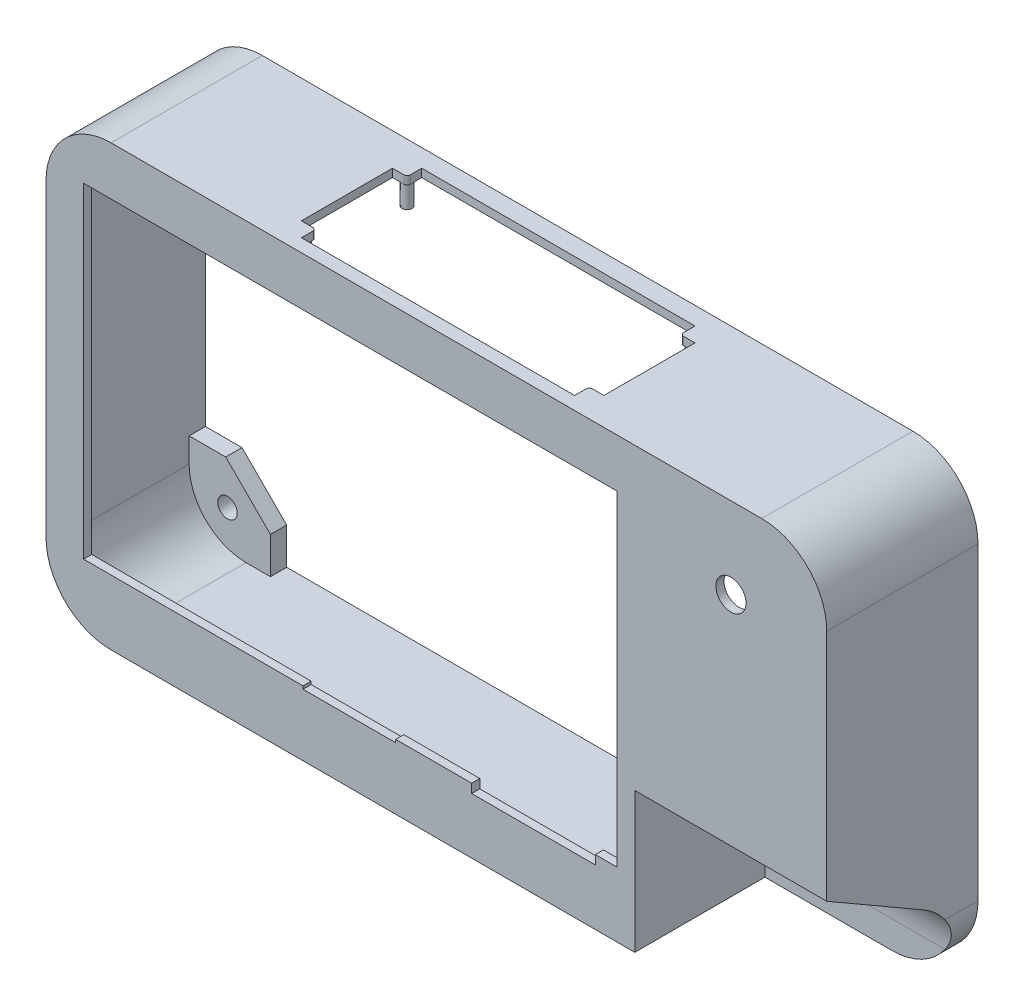
SolidWorks part; units mm, degrees
ref_plane "Front Plane" through (0, 0, 0) normal (0, 0, 1) x (1, 0, 0)
ref_plane "Top Plane" through (0, 0, 0) normal (0, 1, 0) x (1, 0, 0)
ref_plane "Right Plane" through (0, 0, 0) normal (1, 0, 0) x (0, 0, -1)
sketch "Sketch2" plane through (0, 0, 0) normal (0, 0, 1) x (1, 0, 0)
  line L1 (-100, -67.5) -> (100, -67.5)
  line L2 (-120, -47.5) -> (-120, 47.5)
  line L3 (-100, 67.5) -> (100, 67.5)
  line L4 (120, -47.5) -> (120, 47.5)
  line L5 (-120, -67.5) -> (120, 67.5) construction
  line L6 (-120, 67.5) -> (120, -67.5) construction
  arc A0 (100, 67.5) -> (120, 47.5) centre (100, 47.5) cw
  arc A1 (100, -67.5) -> (120, -47.5) centre (100, -47.5) ccw
  arc A2 (-100, -67.5) -> (-120, -47.5) centre (-100, -47.5) cw
  arc A3 (-120, 47.5) -> (-100, 67.5) centre (-100, 47.5) cw
  point P0 (0, 0)
  dimension "D2" = 20
  dimension "D1" = 135
  dimension "25" = 240
extrude "Boss-Extrude1" add sketch "Sketch2" along normal mid plane 80
sketch "Sketch3" plane through (0, 0, 40) normal (0, 0, 1) x (1, 0, 0)
  line L0 (61, -67.5) -> (61, -9.3428)
  line L1 (-100, -67.5) -> (100, -67.5) construction
  line L2 (61, -9.3428) -> (120, -9.3428)
  line L3 (120, -47.5) -> (120, 47.5) construction
  line L4 (120, -9.3428) -> (120, -47.5)
  line L5 (100, -67.5) -> (61, -67.5)
  line L6 (120, -47.5) -> (61, -47.5)
  arc A0 (100, -67.5) -> (120, -47.5) centre (100, -47.5) ccw construction
  arc A1 (100, -67.5) -> (120, -47.5) centre (100, -47.5) ccw
  line M11 (-100, -67.5) -> (100, -67.5)
  arc M12 (100, -67.5) -> (120, -47.5) centre (100, -47.5) ccw
  dimension "D1" = 59
extrude "Cut-Extrude2" cut sketch "Sketch3" against normal blind 40 contours L6 L0 M12 M11 region at (88.5361, -57.0659, 40)
sketch "Sketch4" plane through (120, 0, 0) normal (1, 0, 0) x (0, 0, -1)
  line L0 (0, -47.5) -> (-40, -24.406)
  line L1 (-40, -47.5) -> (-40, 47.5) construction
  line L2 (-40, -47.5) -> (0, -47.5) construction
  line L3 (-40, -24.406) -> (-40, -47.5)
  line L4 (-40, -47.5) -> (0, -47.5)
  dimension "D1" = 30
extrude "Cut-Extrude3" cut sketch "Sketch4" against normal blind 59
shell "Shell2" thickness 2.5 removed face at (0, 0, -40)
sketch "Sketch5" plane through (0, -35.625, 20.5681) normal (0, -0.866, 0.5) x (1, 0, 0)
  line L0 (61, 22.438) -> (120, 22.438) construction
  line L1 (120, -23.75) -> (61, -23.75) construction
  line L3 (78.4748, 17.8994) -> (101.1248, 17.8994)
  line L4 (78.4748, 17.8994) -> (78.4748, 3.7994)
  line L5 (90.5, -0.656) -> (120, -0.656) construction
  line L6 (90.5, -0.656) -> (61, -0.656) construction
  line L9 (120, -23.75) -> (120, 22.438)
  line L10 (120, 22.438) -> (61, 22.438)
  line L11 (61, 22.438) -> (61, -23.75)
  line L12 (61, -23.75) -> (120, -23.75)
  line L13 (120, -23.75) -> (120, -0.656)
  line L14 (120, 22.438) -> (61, 22.438)
  line L15 (61, 22.438) -> (61, -23.75)
  line L16 (61, -23.75) -> (120, -23.75)
  line L19 (78.4748, 3.7994) -> (101.1248, 3.7994)
  line L21 (78.4748, 5.7549) -> (78.4748, 3.7994)
  line L27 (101.1248, 17.8994) -> (101.1248, 3.7994)
  line L35 (101.1248, 5.7549) -> (101.1248, 3.7994)
  line L37 (120, -23.75) -> (120, 22.438) construction
  circle A0 centre (90.5, -0.656) radius 23.094
  dimension "D4" = 18.8752
  dimension "D5" = 17.4748
  dimension "D6" = 18.8752
  dimension "D7" = 17.4748
  dimension "D1" = 0
sketch "Sketch7" plane through (0, -35.625, 20.5681) normal (0, -0.866, 0.5) x (1, 0, 0)
  line L0 (101.1248, 17.8994) -> (101.1248, 3.7994) construction
  line L1 (78.4748, 3.7994) -> (101.1248, 3.7994) construction
  line L2 (78.4748, 17.8994) -> (101.1248, 17.8994) construction
  line L3 (78.4748, 17.8994) -> (78.4748, 3.7994) construction
  line L4 (101.1248, 17.8994) -> (101.1248, 3.7994)
  line L5 (78.4748, 3.7994) -> (101.1248, 3.7994)
  line L6 (78.4748, 17.8994) -> (101.1248, 17.8994)
  line L7 (78.4748, 17.8994) -> (78.4748, 3.7994)
extrude "Cut-Extrude8" cut sketch "Sketch5" against normal blind 5 contours L35 L21 region at (89.7998, -30.2003, 29.964)
sketch "Sketch8" plane through (0, 0, 37.5) normal (0, 0, -1) x (-1, 0, 0)
  line L1 (-105.6, 50.5) -> (-100.6, 50.5)
  line L2 (-105.6, 50.5) -> (-105.6, 55.5)
  line L3 (-105.6, 55.5) -> (-100.6, 55.5)
  line L4 (-100.6, 50.5) -> (-100.6, 55.5)
  line L5 (-103.8071, 52.2929) -> (-102.3929, 53.7071) construction
  line L6 (-58.5, -22.9626) -> (-58.5, -65)
  line L7 (-58.5, -65) -> (100, -65)
  line L8 (117.5, -47.5) -> (117.5, 47.5)
  line L9 (100, 65) -> (-100, 65)
  line L10 (-117.5, 47.5) -> (-117.5, -22.9626)
  line L11 (-117.5, -22.9626) -> (-58.5, -22.9626)
  line L12 (-58.5, -22.9626) -> (-58.5, -65)
  line L13 (-58.5, -65) -> (100, -65)
  line L14 (117.5, -47.5) -> (117.5, 47.5)
  line L15 (100, 65) -> (-100, 65)
  line L16 (-117.5, 47.5) -> (-117.5, -22.9626)
  line L17 (-117.5, -22.9626) -> (-58.5, -22.9626)
  line L18 (-103.8071, 53.7071) -> (-102.3929, 52.2929) construction
  line L19 (-93.1, 50.5) -> (-88.1, 50.5)
  line L20 (-93.1, 50.5) -> (-93.1, 55.5)
  line L21 (-93.1, 55.5) -> (-88.1, 55.5)
  line L22 (-88.1, 50.5) -> (-88.1, 55.5)
  line L23 (-91.3071, 52.2929) -> (-89.8929, 53.7071) construction
  line L24 (-91.3071, 53.7071) -> (-89.8929, 52.2929) construction
  line L25 (-93.1, 29.5) -> (-88.1, 29.5)
  line L26 (-93.1, 29.5) -> (-93.1, 34.5)
  line L27 (-93.1, 34.5) -> (-88.1, 34.5)
  line L28 (-88.1, 29.5) -> (-88.1, 34.5)
  line L29 (-91.3071, 31.2929) -> (-89.8929, 32.7071) construction
  line L30 (-91.3071, 32.7071) -> (-89.8929, 31.2929) construction
  line L31 (-105.6, 29.5) -> (-100.6, 29.5)
  line L32 (-105.6, 29.5) -> (-105.6, 34.5)
  line L33 (-105.6, 34.5) -> (-100.6, 34.5)
  line L34 (-100.6, 29.5) -> (-100.6, 34.5)
  line L35 (-103.8071, 31.2929) -> (-102.3929, 32.7071) construction
  line L36 (-103.8071, 32.7071) -> (-102.3929, 31.2929) construction
  arc A3 (100, -65) -> (117.5, -47.5) centre (100, -47.5) ccw
  arc A4 (117.5, 47.5) -> (100, 65) centre (100, 47.5) ccw
  arc A5 (-100, 65) -> (-117.5, 47.5) centre (-100, 47.5) ccw
  arc A6 (100, -65) -> (117.5, -47.5) centre (100, -47.5) ccw
  arc A7 (117.5, 47.5) -> (100, 65) centre (100, 47.5) ccw
  arc A8 (-100, 65) -> (-117.5, 47.5) centre (-100, 47.5) ccw
  ellipse E0 centre (-90.6, 32) end of major axis (-89.8929, 32.7071) minor radius 1 construction
  ellipse E1 centre (-103.1, 32) end of major axis (-102.3929, 32.7071) minor radius 1 construction
  ellipse E2 centre (-103.1, 53) end of major axis (-102.3929, 53.7071) minor radius 1 construction
  ellipse E3 centre (-90.6, 53) end of major axis (-89.8929, 53.7071) minor radius 1 construction
  ellipse E4 centre (-90.6, 32) end of major axis (-89.8929, 32.7071) minor radius 1
  ellipse E5 centre (-103.1, 32) end of major axis (-102.3929, 32.7071) minor radius 1
  ellipse E6 centre (-103.1, 53) end of major axis (-102.3929, 53.7071) minor radius 1
  ellipse E7 centre (-90.6, 53) end of major axis (-89.8929, 53.7071) minor radius 1
  dimension "D2" = 5
  dimension "D1" = 0
extrude "Boss-Extrude2" add sketch "Sketch8" along normal up to surface (3.1 mm away) contours L1 L4 L3 L2 E6 | L19 L22 L21 L20 E7 | L25 L28 L27 L26 E4 | L31 L34 L33 L32 E5 region at (105.5293, 53, 37.5) region at (93.0293, 53, 37.5) region at (93.0293, 32, 37.5) region at (105.5293, 32, 37.5)
sketch "Sketch9" plane through (0, 0, 40) normal (0, 0, 1) x (1, 0, 0)
  circle A0 centre (90.55, 42.5) radius 4.6353
extrude "Cut-Extrude9" cut sketch "Sketch9" against normal blind 5
sketch "Sketch10" plane through (0, 0, 0) normal (1, 0, 0) x (0, 0, -1)
  line L1 (6.5, 80.3941) -> (74.4591, 80.3941)
  line L2 (6.5, 80.3941) -> (6.5, -88.8754)
  line L3 (6.5, -88.8754) -> (74.4591, -88.8754)
  line L4 (74.4591, 80.3941) -> (74.4591, -88.8754)
  dimension "D1" = 6.5
extrude "Cut-Extrude10" cut sketch "Sketch10" against normal through all both and the other way through all
fillet "Fillet2" radius 20 2 edges at (90.5, -47.5, 0) (88, -46.0566, -2.5)
sketch "Sketch11" plane through (0, 0, 40) normal (0, 0, 1) x (1, 0, 0)
  line L0 (10.85, -47.55) -> (10.85, -47.8) construction
  line L2 (48.85, -47.8) -> (48.85, -47.55) construction
  line L4 (-41, -47.55) -> (-41, -48.45) construction
  line L5 (-41, -48.45) -> (-12.5, -48.45) construction
  line L6 (-12.5, -48.45) -> (-12.5, -47.55) construction
  line L7 (-12.5, -47.55) -> (-41, -47.55) construction
  line L8 (-108.45, -47.55) -> (55.55, -47.55) construction
  line L9 (55.55, -47.55) -> (55.55, 52.55) construction
  line L10 (55.55, 52.55) -> (-108.45, 52.55) construction
  line L11 (-108.45, 52.55) -> (-108.45, -47.55) construction
  line L12 (10.85, -47.55) -> (10.85, -47.8)
  line L14 (48.85, -47.8) -> (48.85, -47.55)
  line L16 (-41, -47.55) -> (-41, -48.45)
  line L17 (-41, -48.45) -> (-12.5, -48.45)
  line L18 (-12.5, -48.45) -> (-12.5, -47.55)
  line L19 (-12.5, -47.55) -> (-41, -47.55)
  line L20 (-108.45, -47.55) -> (10.85, -47.55)
  line L21 (55.55, -47.55) -> (55.55, 52.55)
  line L22 (55.55, 52.55) -> (-108.45, 52.55)
  line L23 (-108.45, 52.55) -> (-108.45, -47.55)
  line L24 (10.85, -47.55) -> (10.85, -50.3)
  line L25 (48.85, -50.3) -> (10.85, -50.3) construction
  line L26 (10.85, -50.3) -> (48.85, -50.3)
  line L27 (48.85, -50.3) -> (48.85, -47.55)
  line L28 (48.85, -47.55) -> (55.55, -47.55)
extrude "Cut-Extrude11" cut sketch "Sketch11" against normal blind 15 contours L14 L28 L21 L22 L23 L20 L19 L12 L24 L26 L27 | L18 L19 L16 L17 region at (-26.0939, 2.1747, 40) region at (-26.75, -48, 40)
sketch "Sketch12" plane through (0, 67.5, 0) normal (0, 1, 0) x (1, 0, 0)
  line L12 (-49.5, -4) -> (-49.5, -31)
  line L13 (-49.5, -31) -> (-46.5, -31)
  line L14 (-45, -32.5) -> (-45, -35.5)
  line L15 (-45, -35.5) -> (38, -35.5)
  line L16 (38, -35.5) -> (38, -32.5)
  line L17 (39.5, -31) -> (42.5, -31)
  line L18 (42.5, -31) -> (42.5, -4)
  line L19 (42.5, -4) -> (39.5, -4)
  line L20 (38, -2.5) -> (38, 0.5)
  line L21 (38, 0.5) -> (-45, 0.5)
  line L22 (-45, 0.5) -> (-45, -2.5)
  line L23 (-46.5, -4) -> (-49.5, -4)
  line L31 (42.5, -4) -> (39.5, -4)
  line L48 (-50, -3.5) -> (-50, -31.5)
  line L49 (-50, -31.5) -> (-46.5, -31.5)
  line L50 (-45.5, -32.5) -> (-45.5, -36)
  line L51 (-45.5, -36) -> (38.5, -36)
  line L52 (38.5, -36) -> (38.5, -32.5)
  line L53 (39.5, -31.5) -> (43, -31.5)
  line L54 (43, -31.5) -> (43, -3.5)
  line L55 (43, -3.5) -> (39.5, -3.5)
  line L56 (38.5, -2.5) -> (38.5, 1)
  line L57 (38.5, 1) -> (-45.5, 1)
  line L58 (-45.5, 1) -> (-45.5, -2.5)
  line L59 (-46.5, -3.5) -> (-50, -3.5)
  line L60 (-50, -3.5) -> (-50, -31.5)
  line L61 (-50, -31.5) -> (-46.5, -31.5)
  line L62 (-45.5, -32.5) -> (-45.5, -36)
  line L63 (-45.5, -36) -> (38.5, -36)
  line L64 (38.5, -36) -> (38.5, -32.5)
  line L65 (39.5, -31.5) -> (43, -31.5)
  line L66 (43, -31.5) -> (43, -3.5)
  line L67 (43, -3.5) -> (39.5, -3.5)
  line L68 (38.5, -2.5) -> (38.5, 1)
  line L69 (38.5, 1) -> (-45.5, 1)
  line L70 (-45.5, 1) -> (-45.5, -2.5)
  line L71 (-46.5, -3.5) -> (-50, -3.5)
  arc A4 (-45, -32.5) -> (-46.5, -31) centre (-46.5, -32.5) ccw
  arc A5 (39.5, -31) -> (38, -32.5) centre (39.5, -32.5) ccw
  arc A6 (38, -2.5) -> (39.5, -4) centre (39.5, -2.5) ccw
  arc A7 (-46.5, -4) -> (-45, -2.5) centre (-46.5, -2.5) ccw
  arc A16 (-45.5, -32.5) -> (-46.5, -31.5) centre (-46.5, -32.5) ccw
  arc A17 (39.5, -31.5) -> (38.5, -32.5) centre (39.5, -32.5) ccw
  arc A18 (38.5, -2.5) -> (39.5, -3.5) centre (39.5, -2.5) ccw
  arc A19 (-46.5, -3.5) -> (-45.5, -2.5) centre (-46.5, -2.5) ccw
  arc A20 (-45.5, -32.5) -> (-46.5, -31.5) centre (-46.5, -32.5) ccw
  arc A21 (39.5, -31.5) -> (38.5, -32.5) centre (39.5, -32.5) ccw
  arc A22 (38.5, -2.5) -> (39.5, -3.5) centre (39.5, -2.5) ccw
  arc A23 (-46.5, -3.5) -> (-45.5, -2.5) centre (-46.5, -2.5) ccw
  dimension "D1" = 0
  dimension "D2" = 0.5
extrude "Cut-Extrude12" cut sketch "Sketch12" against normal blind 7 contours A23 L71 L60 L61 A20 L62 L63 L64 A21 L65 L66 L67 A22 L68 L69 L70 region at (-48.25, 67.5, 3.6001) body kept at (-120, -47.5, 40)
sketch "Sketch13" plane through (0, 65, 0) normal (0, -1, 0) x (1, 0, 0)
  circle A0 centre (40.25, 33.25) radius 1.5 construction
  circle A1 centre (-47.25, 33.25) radius 1.5 construction
  circle A2 centre (-47.25, 1.75) radius 1.5 construction
  circle A3 centre (40.25, 1.75) radius 1.5 construction
  circle A4 centre (40.25, 33.25) radius 1.5
  circle A5 centre (-47.25, 33.25) radius 1.5
  circle A6 centre (-47.25, 1.75) radius 1.5
  circle A7 centre (40.25, 1.75) radius 1.5
extrude "Boss-Extrude3" add sketch "Sketch13" along normal blind 7
sketch "Sketch14" plane through (0, -33.4599, 19.3181) normal (0, 0.866, -0.5) x (1, 0, 0)
  line L1 (101.1248, -3.7994) -> (78.3799, -3.7994)
  line L2 (101.1248, -3.7994) -> (101.1248, -2.4204)
  line L3 (101.1248, -2.4204) -> (78.3799, -2.4204)
  line L4 (78.3799, -3.7994) -> (78.3799, -2.4204)
extrude "Boss-Extrude4" add sketch "Sketch14" along normal blind 16
sketch "Sketch15" plane through (0, 1.8997, 3.2904) normal (0, 0.5, 0.866) x (1, 0, 0)
  circle A0 centre (81.4748, -27.3362) radius 1 construction
  circle A1 centre (98.1248, -27.3362) radius 1 construction
  circle A2 centre (81.4748, -27.3362) radius 1
  circle A3 centre (98.1248, -27.3362) radius 1
extrude "Cut-Extrude13" cut sketch "Sketch15" against normal blind 6
sketch "Sketch16" plane through (0, -19.6035, 11.3181) normal (0, 0.866, -0.5) x (1, 0, 0)
  line L0 (101.1248, -2.4204) -> (78.3799, -2.4204) construction
  line L1 (92.6039, -2.4204) -> (86.9008, -2.4204)
  line L2 (92.6039, -2.4204) -> (92.6039, -3.7994)
  line L3 (92.6039, -3.7994) -> (86.9008, -3.7994)
  line L4 (86.9008, -2.4204) -> (86.9008, -3.7994)
  line L5 (78.3799, -3.7994) -> (101.1248, -3.7994) construction
  line L6 (101.1248, -2.4204) -> (92.6039, -2.4204) construction
  line L7 (86.9008, -2.4204) -> (78.3799, -2.4204) construction
sketch "Sketch17" plane through (0, 1.2102, 2.0962) normal (0, -0.5, -0.866) x (-1, 0, 0)
  line L0 (-78.3799, -22.6362) -> (-78.3799, -38.6362) construction
  line L1 (-98.1248, -35.6362) -> (-81.3799, -35.6362)
  line L2 (-98.1248, -35.6362) -> (-98.1248, -30.6651)
  line L3 (-98.1248, -30.6651) -> (-81.3799, -30.6651)
  line L4 (-81.3799, -35.6362) -> (-81.3799, -30.6651)
  line L5 (-101.1248, -22.6362) -> (-101.1248, -38.6362) construction
  line L7 (-117.5, -38.6362) -> (-58.5, -38.6362) construction
  line L8 (-101.1248, -22.6362) -> (-78.3799, -22.6362) construction
  line L9 (-95.6248, -30.6651) -> (-83.9748, -30.6651)
  line L10 (-95.6248, -30.6651) -> (-95.6248, -25.6362)
  line L11 (-95.6248, -25.6362) -> (-83.9748, -25.6362)
  line L12 (-83.9748, -30.6651) -> (-83.9748, -25.6362)
  circle A1 centre (-98.1248, -27.3362) radius 1 construction
  circle A2 centre (-81.4748, -27.3362) radius 1 construction
  dimension "D5" = 2.5
  dimension "D1" = 3
  dimension "D2" = 3
  dimension "D3" = 3
  dimension "D4" = 3
  dimension "D6" = 2.5
extrude "Cut-Extrude14" cut sketch "Sketch17" against normal blind 6 contours L1 L4 L3 L2 | L3 L12 L11 L10 region at (89.7523, -27.4991, 18.6715) region at (89.7998, -23.169, 16.1715)
extrude "Boss-Extrude5" add sketch "Sketch16" along normal blind 25
sketch "Sketch19" plane through (86.9008, 0, 0) normal (-1, 0, 0) x (0, 0, 1)
  line L0 (3.4143, -1.0728) -> (4.6085, -0.3833)
  line L1 (0.9143, 3.2573) -> (13.4143, -18.3933) construction
  line L2 (2.1085, 3.9468) -> (14.6085, -17.7038) construction
  line L3 (4.6085, -0.3833) -> (2.1085, 3.9468)
  line L4 (2.1085, 3.9468) -> (0.9143, 3.2573)
  line L5 (0.9143, 3.2573) -> (3.4143, -1.0728)
  dimension "D1" = 5
extrude "Boss-Extrude6" add sketch "Sketch19" along normal blind 8 and the other way blind 14
sketch "Sketch20" plane through (0, 2.0471, -1.1819) normal (0, 0.866, -0.5) x (1, 0, 0)
  line L0 (78.9008, -3.7994) -> (100.9008, -3.7994) construction
  line L1 (100.9008, -2.4204) -> (95.9008, -2.4204)
  line L2 (100.9008, -2.4204) -> (100.9008, -3.7994)
  line L3 (100.9008, -3.7994) -> (95.9008, -3.7994)
  line L4 (95.9008, -2.4204) -> (95.9008, -3.7994)
  line L6 (78.9008, -2.4204) -> (83.9008, -2.4204)
  line L7 (78.9008, -2.4204) -> (78.9008, -3.7994)
  line L8 (78.9008, -3.7994) -> (83.9008, -3.7994)
  line L9 (83.9008, -2.4204) -> (83.9008, -3.7994)
  dimension "D1" = 5
  dimension "D2" = 5
extrude "Boss-Extrude7" add sketch "Sketch20" along normal blind 8
sketch "Sketch21" plane through (0, 1.8997, 3.2904) normal (0, 0.5, 0.866) x (1, 0, 0)
  circle A0 centre (81.4748, 7.6638) radius 1 construction
  circle A1 centre (98.1248, 7.6638) radius 1 construction
  circle A2 centre (81.4748, 7.6638) radius 1
  circle A3 centre (98.1248, 7.6638) radius 1
extrude "Cut-Extrude15" cut sketch "Sketch21" against normal blind 8
sketch "Sketch22" plane through (0, 0, -6.5) normal (0, 0, -1) x (-1, 0, 0)
  line L2 (-120, -40) -> (-106.25, -40)
  line L5 (-92.5, -53.75) -> (-92.5, -67.5)
  line L7 (-92.5, -67.5) -> (-100, -67.5)
  line L8 (-120, -40) -> (-120, -47.5)
  line L9 (100, -67.5) -> (-100, -67.5) construction
  line L10 (-105.7106, -53.2106) -> (-103.5893, -51.0893) construction
  line L11 (-106.25, -40) -> (-92.5, -53.75)
  arc A0 (-120, -47.5) -> (-100, -67.5) centre (-100, -47.5) ccw construction
  arc A1 (-120, -47.5) -> (-100, -67.5) centre (-100, -47.5) ccw
  circle A2 centre (-105.7106, -53.2106) radius 3
  dimension "D2" = 27.5
extrude "Boss-Extrude8" add sketch "Sketch22" against normal blind 5
mirror "Mirror2" about plane through (0, 0, 0) normal (0, 1, 0) of "Boss-Extrude8"
mirror "Mirror3" about plane through (0, 0, 0) normal (1, 0, 0) of "Boss-Extrude8", "Mirror2"
sketch "Sketch23" plane through (0, 0, 40) normal (0, 0, 1) x (1, 0, 0)
  line L0 (108.4881, 126.8595) -> (308.4881, 126.8595) construction
